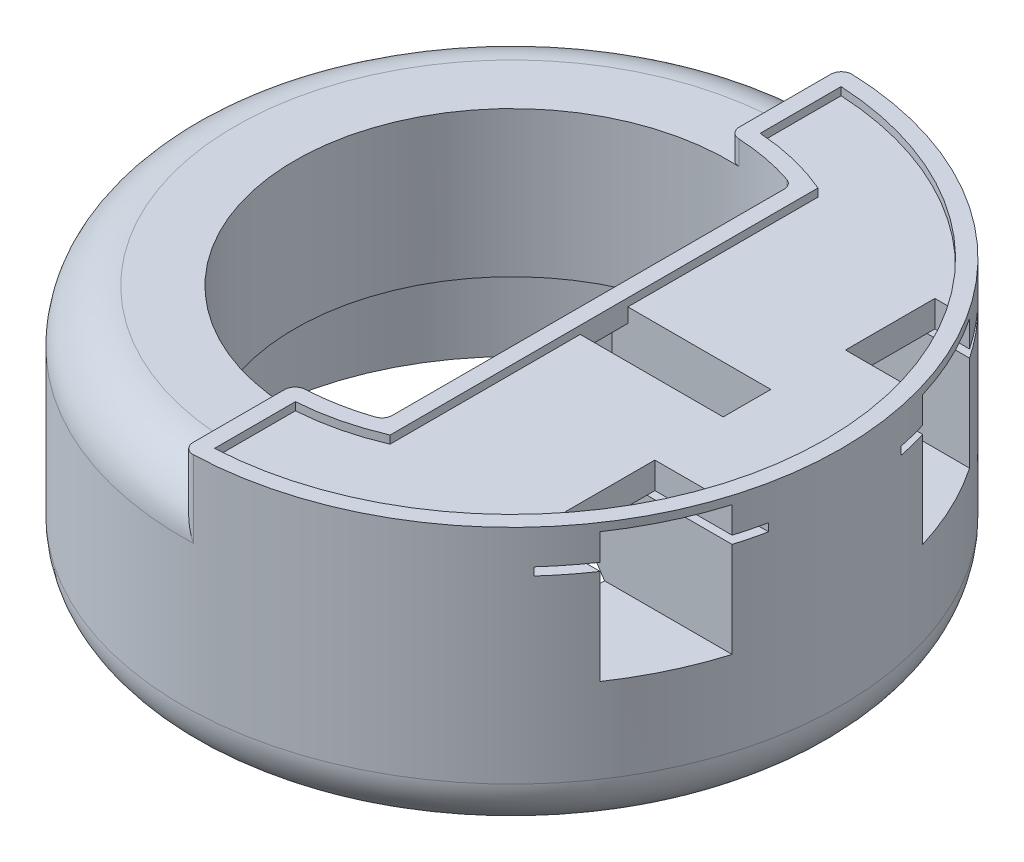
SolidWorks part; units mm, degrees
ref_plane "Plano frontal" through (0, 0, 0) normal (0, 0, 1) x (1, 0, 0)
ref_plane "Plano superior" through (0, 0, 0) normal (0, 1, 0) x (1, 0, 0)
ref_plane "Plano direito" through (0, 0, 0) normal (1, 0, 0) x (0, 0, -1)
sketch "Esboço1" plane through (0, 0, 0) normal (0, 1, 0) x (1, 0, 0)
  line L0 (14.4, 45.0022) -> (14.4, -45.0022)
  arc A0 (14.4, -45.0022) -> (14.4, 45.0022) centre (0, 0) ccw
  dimension "D1" = 94.5
  dimension "D2" = 14.4
extrude "Ressalto-extrusão1" add sketch "Esboço1" along normal blind 5
sketch "Esboço2" plane through (0, 5, 0) normal (0, 1, 0) x (1, 0, 0)
  line L0 (14.4, 4.5) -> (44.4, 4.5)
  line L1 (14.4, 45.0022) -> (14.4, -45.0022) construction
  line L2 (44.4, 4.5) -> (44.4, -4.5)
  line L3 (44.4, -4.5) -> (14.4, -4.5)
  line L4 (14.4, -4.5) -> (14.4, 4.5)
  line L5 (14.4, 0) -> (47.25, 0) construction
  arc A1 (14.4, -45.0022) -> (14.4, 45.0022) centre (0, 0) ccw construction
  dimension "D1" = 9
  dimension "D2" = 30
extrude "Corte-extrusão1" cut sketch "Esboço2" against normal through all
sketch "Esboço3" plane through (0, 0, 0) normal (0, 0, 1) x (1, 0, 0)
  line L0 (47.189, 0) -> (42.8221, -13)
  line L1 (14.4, 0) -> (47.25, 0) construction
  line L2 (32.189, -5.4942) -> (35.189, 0)
  line L3 (36.6836, -13.0289) -> (42.8221, -13)
  line L4 (35.189, 0) -> (47.189, 0)
  arc A0 (32.189, -5.4942) -> (36.6836, -13.0289) centre (36.6596, -7.9353) ccw
  circle A2 centre (36.6596, -7.9353) radius 2.35
  dimension "D1" = 12
  dimension "D2" = 13
  dimension "D3" = 3
extrude "Ressalto-extrusão2" add sketch "Esboço3" along normal blind 8 from offset 4.5
mirror "Espelhar1" about plane through (0, 0, 0) normal (0, 0, 1) of "Ressalto-extrusão2"
sketch "Esboço4" plane through (0, 5, 0) normal (0, 1, 0) x (1, 0, 0)
  line L0 (14.4, 45.0022) -> (15.9238, 49.7644)
  line L1 (14.4, -45.0022) -> (15.9238, -49.7644)
  arc A0 (14.4, -45.0022) -> (14.4, 45.0022) centre (0, 0) ccw construction
  arc A1 (14.4, -45.0022) -> (14.4, 45.0022) centre (0, 0) ccw
  arc A2 (15.9238, -49.7644) -> (15.9238, 49.7644) centre (0, 0) ccw
  dimension "D1" = 5
extrude "Corte-extrusão2" cut sketch "Esboço4" against normal through all
fillet "Filete1" radius 5 2 edges at (42.8221, -13, -8.5) (42.8221, -13, 8.5)
chamfer "Chanfro1" [suppressed] distance 5 angle 45
sketch "Esboço5" [suppressed] plane through (0, 0, 0) normal (0, 0, 1) x (1, 0, 0)
  line L0 (16.9, 2.5) -> (16.9, 0)
  line L1 (19.4, 5) -> (14.4, 0) construction
  line L2 (14.4, 0) -> (45.5666, 0) construction
  line L3 (16.9, 0) -> (14.4, 0)
  line L4 (14.4, 0) -> (16.9, 2.5)
  dimension "D1" = 2.5
extrude "Corte-extrusão3" [suppressed] cut sketch "Esboço5" against normal through all both and the other way through all
ref_plane "Plano1" through (0, -5.5, 0) normal (0, -1, 0) x (-1, 0, 0)
sketch "Esboço7" plane through (0, -5.5, 0) normal (0, -1, 0) x (-1, 0, 0)
  line L0 (-14.5, 44.9701) -> (-14.5, 4.5)
  line L1 (-33.5473, -4.5) -> (-33.5473, -33.2738)
  line L2 (-14.4, -4.5) -> (-44.4, -4.5) construction
  line L3 (-33.5473, 4.5) -> (-33.5473, 33.2738)
  line L4 (-44.4, 4.5) -> (-14.4, 4.5) construction
  line L5 (-33.5473, 4.5) -> (-14.5, 4.5)
  line L6 (-33.5473, -4.5) -> (-14.5, -4.5)
  line L7 (-14.5, -4.5) -> (-14.5, -44.9701)
  arc A0 (-14.5, 44.9701) -> (-33.5473, 33.2738) centre (0, 0) ccw
  arc A1 (-33.5473, -33.2738) -> (-14.5, -44.9701) centre (0, 0) ccw
  dimension "D1" = 94.5
  dimension "D2" = 14.5
  dimension "D3" = 19.0473
extrude "Ressalto-extrusão4" add sketch "Esboço7" along normal blind 20
sketch "Esboço8" plane through (0, -25.5, 0) normal (0, -1, 0) x (1, 0, 0)
  line L0 (33.5473, -33.2738) -> (33.5473, 33.2738)
  line L2 (14.5, 44.9701) -> (14.5, -44.9701)
  arc A0 (33.5473, 33.2738) -> (14.5, 44.9701) centre (0, 0) ccw
  arc A1 (14.5, -44.9701) -> (33.5473, -33.2738) centre (0, 0) ccw
  dimension "D1" = 94.5
  dimension "D2" = 33.5473
extrude "Ressalto-extrusão5" add sketch "Esboço8" against normal blind 4
sketch "Esboço9" plane through (0, -25.5, 0) normal (0, -1, 0) x (1, 0, 0)
  line L0 (33.5473, -33.2738) -> (33.5473, 33.2738) construction
  line L1 (33.5473, -33.2738) -> (33.5473, 33.2738)
  arc A0 (14.4, -45.0022) -> (45.5666, -12.5) centre (0, 0) ccw construction
  arc A1 (45.5666, -12.5) -> (47.0352, -4.5) centre (0, 0) ccw construction
  arc A2 (47.0352, -4.5) -> (47.0352, 4.5) centre (0, 0) ccw construction
  arc A3 (47.0352, 4.5) -> (45.5666, 12.5) centre (0, 0) ccw construction
  arc A4 (45.5666, 12.5) -> (14.4, 45.0022) centre (0, 0) ccw construction
  arc A5 (33.5473, -33.2738) -> (45.5666, -12.5) centre (0, 0) ccw
  arc A6 (45.5666, -12.5) -> (47.0352, -4.5) centre (0, 0) ccw
  arc A7 (47.0352, -4.5) -> (47.0352, 4.5) centre (0, 0) ccw
  arc A8 (47.0352, 4.5) -> (45.5666, 12.5) centre (0, 0) ccw
  arc A9 (45.5666, 12.5) -> (33.5473, 33.2738) centre (0, 0) ccw
extrude "Ressalto-extrusão6" add sketch "Esboço9" against normal up to surface (4 mm away) up to face at (24.0236, -21.5, 0)
fillet "Filete2" radius 5 2 edges at (33.5473, -11.9675, -8.5) (33.5473, -11.9675, 8.5)
sketch "Esboço10" plane through (0, 0, 0) normal (0, 0, 1) x (1, 0, 0)
  line L0 (14.5, -10.5) -> (24.5, -25.5)
  line L1 (24.5, -25.5) -> (14.5, -25.5)
  line L3 (14.5, -25.5) -> (14.5, -10.5)
  dimension "D1" = 10
  dimension "D2" = 15
  dimension "D3" = 56.31
extrude "Corte-extrusão4" cut sketch "Esboço10" against normal through all both and the other way through all
sketch "Esboço12" plane through (0, -25.5, 0) normal (0, -1, 0) x (1, 0, 0)
  circle A0 centre (0, 0) radius 65
  circle A1 centre (0, 0) radius 41
  dimension "D1" = 130
  dimension "D2" = 24
extrude "Ressalto-extrusão7" add sketch "Esboço12" against normal up to surface (20 mm away) up to face at (26.8613, -5.5, -18.8977)
sketch "Esboço13" plane through (0, -5.5, 0) normal (0, 1, 0) x (1, 0, 0)
  line L0 (33.5473, 12.5) -> (39.048, 12.5)
  line L1 (33.5473, 23.5707) -> (33.5473, 12.5) construction
  line L2 (33.5473, 23.5707) -> (33.5473, 12.5)
  line L3 (0, 0) -> (-33.611, 0) construction
  line L4 (33.5473, -23.5707) -> (33.5473, -12.5)
  line L5 (33.5473, -12.5) -> (39.048, -12.5)
  arc A0 (39.048, 12.5) -> (33.5473, 23.5707) centre (0, 0) ccw construction
  arc A1 (39.048, 12.5) -> (33.5473, 23.5707) centre (0, 0) ccw
  arc A2 (39.048, -12.5) -> (33.5473, -23.5707) centre (0, 0) cw
extrude "Ressalto-extrusão8" add sketch "Esboço13" against normal up to surface (20 mm away) up to face at (-8.25, -25.5, 0)
sketch "Esboço14" plane through (0, 5, 0) normal (0, 1, 0) x (1, 0, 0)
  line L0 (14.4, 45.0022) -> (14.4, 60.5616)
  line L1 (14.4, -45.0022) -> (14.4, -60.5616)
  arc A0 (14.4, -45.0022) -> (14.4, 45.0022) centre (0, 0) ccw construction
  arc A1 (14.4, -45.0022) -> (14.4, 45.0022) centre (0, 0) ccw
  arc A2 (14.4, -60.5616) -> (14.4, 60.5616) centre (0, 0) ccw
  arc A3 (18.9714, -59.2887) -> (18.9714, 59.2887) centre (0, 0) ccw construction
  dimension "D1" = 15
extrude "Ressalto-extrusão9" add sketch "Esboço14" against normal up to surface (5 mm away) up to face at (29.7731, 0, -16.5908)
sketch "Esboço16" plane through (0, -5.5, 0) normal (0, 1, 0) x (1, 0, 0)
  line L0 (14.4, 60.5616) -> (14.4, 4.5) construction
  line L1 (14.4, 60.5616) -> (14.4, 38.388)
  line L2 (14.4, -4.5) -> (14.4, -60.5616) construction
  line L3 (14.4, -38.388) -> (14.4, -60.5616)
  arc A0 (14.4, 60.5616) -> (14.4, -60.5616) centre (0, 0) ccw
  arc A1 (14.4, 38.388) -> (14.4, -38.388) centre (0, 0) ccw
  dimension "D1" = 41
extrude "Ressalto-extrusão10" add sketch "Esboço16" along normal up to surface (10.5 mm away) up to face at (32.375, 5, 0)
sketch "Esboço17" plane through (0, -5.5, 0) normal (0, 1, 0) x (1, 0, 0)
  circle A0 centre (0, 0) radius 62.25
  circle A1 centre (0, 0) radius 65 construction
  circle A2 centre (0, 0) radius 65
  dimension "D1" = 124.5
extrude "Corte-extrusão5" cut sketch "Esboço17" against normal through all
sketch "Esboço18" plane through (0, 5, 0) normal (0, 1, 0) x (1, 0, 0)
  line L0 (39.0096, 4.5) -> (44.4, 4.5)
  line L1 (44.4, -4.5) -> (44.4, 4.5) construction
  line L2 (45.3415, 4.5) -> (40.7523, 4.5) construction
  line L3 (44.4, 4.5) -> (44.4, -4.5)
  line L4 (44.4, -4.5) -> (39.0096, -4.5)
  line L6 (39.0096, 4.5) -> (39.0096, -4.5)
extrude "Corte-extrusão6" cut sketch "Esboço18" against normal up to surface (26.5 mm away) up to face at (32.238, -21.5, 0)
sketch "Esboço19" plane through (0, -5.5, 0) normal (0, 1, 0) x (1, 0, 0)
  line L0 (14.4, 4.5) -> (35.189, 4.5)
  line L4 (14.4, 4.5) -> (14.4, 38.388)
  line L5 (0, 0) -> (-73.7053, 0) construction
  line L6 (14.4, -4.5) -> (35.189, -4.5)
  line L8 (14.4, -4.5) -> (14.4, -38.388)
  line L9 (35.189, -4.5) -> (35.189, -21.0413)
  line L11 (35.189, 4.5) -> (35.189, 21.0413)
  arc A0 (24.5, 32.8748) -> (14.5, 38.3504) centre (0, 0) ccw construction
  arc A1 (35.189, 21.0413) -> (14.4, 38.388) centre (0, 0) ccw
  arc A2 (35.189, -21.0413) -> (14.4, -38.388) centre (0, 0) cw
extrude "Ressalto-extrusão12" add sketch "Esboço19" along normal up to surface (5.5 mm away) separate body up to face at (34.3346, 0, 0)
sketch "Esboço20" plane through (0, 5, 0) normal (0, 1, 0) x (1, 0, 0)
  circle A0 centre (0, 0) radius 62.25
extrude "Corte-extrusão7" cut sketch "Esboço20" against normal blind 3
sketch "Esboço21" plane through (0, 2, 0) normal (0, 1, 0) x (1, 0, 0)
  line L0 (0, -41) -> (0, -62.25)
  line L1 (0, 0) -> (-62.25, 0) construction
  line L2 (0, 41) -> (0, 62.25)
  line L3 (14.4, 4.5) -> (44.4, 4.5) construction
  line L4 (14.4, 38.388) -> (14.4, 4.5) construction
  line L5 (44.4, -4.5) -> (14.4, -4.5) construction
  line L6 (14.4, -4.5) -> (14.4, -38.388) construction
  line L7 (14.4, 4.5) -> (44.4, 4.5)
  line L8 (14.4, 38.388) -> (14.4, 4.5)
  line L9 (44.4, -4.5) -> (14.4, -4.5)
  line L10 (14.4, -4.5) -> (14.4, -38.388)
  line L11 (44.4, -4.5) -> (44.4, 4.5)
  arc A0 (0, -62.25) -> (0, 62.25) centre (0, 0) ccw
  arc A1 (14.4, 38.388) -> (14.4, -38.388) centre (0, 0) ccw construction
  arc A2 (14.4, 38.388) -> (0, 41) centre (0, 0) ccw
  arc A3 (0, -41) -> (14.4, -38.388) centre (0, 0) ccw
extrude "Ressalto-extrusão13" add sketch "Esboço21" along normal blind 3 contours L0 A0 L2 A2 L8 L7 L11 L9 L10 A3
sketch "Esboço23" plane through (0, -5.5, 0) normal (0, 1, 0) x (1, 0, 0)
  line L0 (51.5592, -34.8814) -> (16, -35)
  line L1 (16, -35) -> (16, -18)
  line L2 (16, -18) -> (66, -18)
  line L3 (66, -18) -> (66, -35)
  line L4 (66, -35) -> (51.5592, -34.8814)
  arc A0 (14.4, -60.5616) -> (14.4, 60.5616) centre (0, 0) ccw construction
extrude "Corte-extrusão8" cut sketch "Esboço23" against normal blind 14 and the other way up to surface other way up to face at (34.3346, 0, 0)
sketch "Esboço24" plane through (0, -5.5, 0) normal (0, -1, 0) x (1, 0, 0)
  line L0 (20.5, 18) -> (10.5, 18)
  line L1 (10.5, 18) -> (10.5, 34.985)
  line L2 (10.5, 34.985) -> (20.5, 34.985)
  line L3 (20.5, 34.985) -> (20.5, 18)
  dimension "D1" = 10
extrude "Corte-extrusão9" cut sketch "Esboço24" along normal up to surface (14 mm away) up to face at (38.1968, -19.5, 26.5424)
sketch "Esboço25" plane through (0, -5.5, 0) normal (0, -1, 0) x (1, 0, 0)
  line L0 (14.5, 18) -> (35.189, 18)
  line L1 (59.5908, 18) -> (14.5, 18) construction
  line L2 (35.189, 21.0413) -> (35.189, 4.5) construction
  line L3 (35.189, 18) -> (35.189, 21.0413)
  line L4 (14.5, 18) -> (14.5, 34.985)
  line L5 (14.5, 34.985) -> (21.3927, 34.9765)
  arc A0 (35.189, 21.0413) -> (14.4, 38.388) centre (0, 0) ccw construction
  arc A1 (35.189, 21.0413) -> (21.3927, 34.9765) centre (0, 0) ccw
extrude "Corte-extrusão10" cut sketch "Esboço25" against normal up to surface (5.5 mm away) up to face at (34.3346, 0, 0)
sketch "Esboço26" plane through (14.5, 0, 0) normal (1, 0, 0) x (0, 0, -1)
  line L0 (-34.9765, 0) -> (-18, 0)
  line L1 (-18, 0) -> (-18, -5.5)
  line L2 (-26.3175, -5.5) -> (26.3175, -5.5) construction
  line L3 (-18, 0) -> (-18, -5.5) construction
  line L4 (-18, -5.5) -> (-34.985, -5.5)
  line L5 (-34.985, 0) -> (-34.985, -5.5) construction
  line L6 (-34.985, -5.5) -> (-34.9765, 0)
extrude "Corte-extrusão11" cut sketch "Esboço26" against normal blind 5
sketch "Esboço27" plane through (0, -5.5, 0) normal (0, 1, 0) x (1, 0, 0)
  line L0 (35.189, -12.5) -> (14.4, -12.5)
  line L1 (14.4, -4.5) -> (14.4, -38.388) construction
  line L2 (14.4, -12.5) -> (14.4, -38.388)
  line L3 (35.189, -12.5) -> (39.048, -12.5)
  arc A0 (14.4, -38.388) -> (21.3927, -34.9765) centre (0, 0) ccw construction
  arc A1 (14.4, -38.388) -> (39.048, -12.5) centre (0, 0) ccw
extrude "Corte-extrusão12" cut sketch "Esboço27" along normal up to surface (5.5 mm away) up to face at (34.3346, 0, 0)
mirror "Espelhar3" about plane through (0, 0, 0) normal (0, 0, 1) of "Corte-extrusão8"
mirror "Espelhar4" about plane through (0, 0, 0) normal (0, 0, 1) of "Corte-extrusão9"
sketch "Esboço28" plane through (0, 0, -12.5) normal (0, 0, -1) x (-1, 0, 0)
  line L0 (-35.189, 0) -> (-35.189, -5.5)
  line L1 (-26.3175, -5.5) -> (26.3175, -5.5) construction
  line L2 (-35.189, 0) -> (-35.189, -5.5) construction
  line L3 (-35.189, -5.5) -> (-8.0032, -5.5)
  line L4 (-8.0032, -5.5) -> (-8.0032, 0)
  line L5 (-8.0032, 0) -> (-35.189, 0)
  dimension "D1" = 27.1857
extrude "Corte-extrusão13" cut sketch "Esboço28" along normal up to vertex (25.888 mm away) up to point (14.4, -5.5, -38.388)
sketch "Esboço29" plane through (0, 5, 0) normal (0, 1, 0) x (1, 0, 0)
  line L0 (63, 34.88) -> (45, 34.88)
  line L1 (45, 34.88) -> (45, 18)
  line L2 (45, 18) -> (63, 18)
  line L3 (63, 18) -> (63, 34.88)
  line L4 (0, 0) -> (66.1862, 0) construction
  line L5 (63, -18) -> (63, -34.88)
  line L6 (45, -18) -> (63, -18)
  line L7 (45, -34.88) -> (45, -18)
  line L8 (63, -34.88) -> (45, -34.88)
  dimension "D1" = 16.88
  dimension "D2" = 18
  dimension "D3" = 18
  dimension "D4" = 45
extrude "Corte-extrusão14" cut sketch "Esboço29" against normal up to surface (5 mm away) up to face at (34.3346, 0, 0)
sketch "Esboço30" plane through (0, 5, 0) normal (0, 1, 0) x (1, 0, 0)
  line L1 (3, 59.174) -> (3, 43.8976)
  line L2 (17.4, 40.4134) -> (17.4, 7.5)
  line L6 (17.4, 7.5) -> (17.4, -40.4134)
  line L7 (3, -43.8976) -> (3, -59.174)
  line L13 (45, 34.88) -> (51.5601, 34.88)
  line L14 (0, 62.25) -> (0, 41)
  line L15 (14.4, 38.388) -> (14.4, 4.5)
  line L16 (14.4, 4.5) -> (44.4, 4.5)
  line L17 (44.4, 4.5) -> (44.4, -4.5)
  line L18 (44.4, -4.5) -> (14.4, -4.5)
  line L19 (14.4, -4.5) -> (14.4, -38.388)
  line L20 (0, -41) -> (0, -62.25)
  line L21 (51.5601, -34.88) -> (45, -34.88)
  line L22 (45, -34.88) -> (45, -18)
  line L23 (45, -18) -> (59.5908, -18)
  line L24 (59.5908, 18) -> (45, 18)
  line L25 (45, 18) -> (45, 34.88)
  line L27 (0, 62.25) -> (0, 41)
  line L28 (14.4, 38.388) -> (14.4, 4.5)
  line L32 (14.4, 4.5) -> (14.4, -38.388)
  line L33 (0, -41) -> (0, -62.25)
  line L39 (14.4, -4.5) -> (14.4, -38.388) construction
  line L40 (17.4, -7.5) -> (17.4, -40.4134) construction
  line L52 (44.4, -4.5) -> (14.4, -4.5) construction
  line L53 (47.4, -7.5) -> (17.4, -7.5) construction
  line L54 (47.4, 7.5) -> (47.4, -7.5) construction
  line L55 (44.4, 4.5) -> (44.4, -4.5) construction
  line L56 (14.4, 4.5) -> (44.4, 4.5) construction
  line L57 (17.4, 7.5) -> (47.4, 7.5) construction
  line L60 (51.5601, -34.88) -> (45, -34.88) construction
  line L61 (45.5595, -37.88) -> (42, -37.88) construction
  line L62 (42, -37.88) -> (42, -15) construction
  line L63 (45, -34.88) -> (45, -18) construction
  line L64 (45, -18) -> (59.5908, -18) construction
  line L65 (42, -15) -> (57.3198, -15) construction
  line L66 (57.3198, 15) -> (42, 15) construction
  line L67 (42, 15) -> (42, 37.88) construction
  line L68 (59.5908, 18) -> (45, 18) construction
  line L69 (45, 18) -> (45, 34.88) construction
  line L70 (42, 37.88) -> (45.5595, 37.88) construction
  line L71 (45, 34.88) -> (51.5601, 34.88) construction
  arc A0 (57.3198, 15) -> (3, 59.174) centre (0, 0) ccw
  arc A1 (17.4, 40.4134) -> (3, 43.8976) centre (0, 0) ccw
  arc A2 (3, -43.8976) -> (17.4, -40.4134) centre (0, 0) ccw
  arc A3 (3, -59.174) -> (57.3198, -15) centre (0, 0) ccw
  arc A4 (57.3198, -15) -> (57.3198, 15) centre (0, 0) ccw
  arc A5 (51.5601, 34.88) -> (0, 62.25) centre (0, 0) ccw
  arc A6 (14.4, 38.388) -> (0, 41) centre (0, 0) ccw
  arc A7 (0, -41) -> (14.4, -38.388) centre (0, 0) ccw
  arc A8 (0, -62.25) -> (51.5601, -34.88) centre (0, 0) ccw
  arc A9 (59.5908, -18) -> (59.5908, 18) centre (0, 0) ccw
  arc A10 (59.5908, 18) -> (0, 62.25) centre (0, 0) ccw
  arc A11 (14.4, 38.388) -> (0, 41) centre (0, 0) ccw
  arc A12 (0, -41) -> (14.4, -38.388) centre (0, 0) ccw
  arc A13 (0, -62.25) -> (59.5908, -18) centre (0, 0) ccw
  arc A14 (59.5908, -18) -> (59.5908, 18) centre (0, 0) ccw
  arc A15 (51.5601, 34.88) -> (0, 62.25) centre (0, 0) ccw construction
  arc A16 (45.5595, 37.88) -> (3, 59.174) centre (0, 0) ccw construction
  arc A17 (0, -62.25) -> (51.5601, -34.88) centre (0, 0) ccw construction
  arc A18 (3, -59.174) -> (45.5595, -37.88) centre (0, 0) ccw construction
  dimension "D1" = 0
  dimension "D2" = 3
extrude "Ressalto-extrusão15" add sketch "Esboço30" along normal blind 1.5
sketch "Esboço31" plane through (0, -5.5, 0) normal (0, 1, 0) x (1, 0, 0)
  line L5 (16, -34.985) -> (14.5, -34.985)
  line L6 (14.5, -34.985) -> (14.5, -38.3504)
  line L7 (14.4, -38.388) -> (14.4, -60.5616)
  line L8 (51.5592, -34.8814) -> (16, -35)
  line L9 (16, -35) -> (16, -34.985)
  line L10 (16, -34.985) -> (14.5, -34.985)
  line L11 (14.5, -34.985) -> (14.5, -38.3504)
  line L12 (14.4, -38.388) -> (14.4, -60.5616)
  line L13 (51.5592, -34.8814) -> (16, -35)
  line L14 (16, -35) -> (16, -34.985)
  line L15 (14.5, 38.3504) -> (14.5, 34.985)
  line L16 (14.5, 34.985) -> (16, 34.985)
  line L17 (16, 34.985) -> (16, 35)
  line L18 (16, 35) -> (51.5592, 34.8814)
  line L19 (14.4, 60.5616) -> (14.4, 38.388)
  line L20 (14.5, 38.3504) -> (14.5, 34.985)
  line L21 (14.5, 34.985) -> (16, 34.985)
  line L22 (16, 34.985) -> (16, 35)
  line L23 (16, 35) -> (51.5592, 34.8814)
  line L24 (14.4, 60.5616) -> (14.4, 38.388)
  arc A2 (14.4, -38.388) -> (14.5, -38.3504) centre (0, 0) ccw
  arc A3 (14.4, -60.5616) -> (51.5592, -34.8814) centre (0, 0) ccw
  arc A4 (14.4, -38.388) -> (14.5, -38.3504) centre (0, 0) ccw
  arc A5 (14.4, -60.5616) -> (51.5592, -34.8814) centre (0, 0) ccw
  arc A6 (51.5592, 34.8814) -> (14.4, 60.5616) centre (0, 0) ccw
  arc A7 (14.5, 38.3504) -> (14.4, 38.388) centre (0, 0) ccw
  arc A8 (51.5592, 34.8814) -> (14.4, 60.5616) centre (0, 0) ccw
  arc A9 (14.5, 38.3504) -> (14.4, 38.388) centre (0, 0) ccw
  dimension "D1" = 0
  dimension "D2" = 0
extrude "Ressalto-extrusão16" add sketch "Esboço31" along normal blind 4
sketch "Esboço32" plane through (0, -1.5, 0) normal (0, 1, 0) x (1, 0, 0)
  line L0 (51.5601, -34.88) -> (51.5601, -41.8803) construction
  line L1 (46.0554, -41.8803) -> (14.4, -41.8803)
  line L2 (14.4, -38.388) -> (14.4, -60.5616) construction
  line L3 (14.4, -41.8803) -> (14.4, -60.5616)
  line L4 (46.0554, -41.8803) -> (51.5601, -41.8803) construction
  arc A1 (0, -62.25) -> (0, 62.25) centre (0, 0) ccw construction
  arc A2 (14.4, -60.5616) -> (46.0554, -41.8803) centre (0, 0) ccw
  arc A3 (51.5601, -34.88) -> (0, 62.25) centre (0, 0) ccw
  line M10 (14.4, -38.388) -> (14.4, -60.5616)
  arc M11 (14.4, -60.5616) -> (51.5592, -34.8814) centre (0, 0) ccw
  dimension "D1" = 7.0003
extrude "Ressalto-extrusão17" add sketch "Esboço32" along normal up to surface (1.5 mm away) contours L1 M11 M10 region at (26.0479, -1.5, 48.8714) up to face at (37.9704, 0, 0)
mirror "Espelhar5" about plane through (0, 0, 0) normal (0, 0, 1) of "Ressalto-extrusão16", "Ressalto-extrusão17"
sketch "Esboço33" plane through (0, -5.5, 0) normal (0, 1, 0) x (1, 0, 0)
  line L15 (59.5908, 18) -> (14.5, 18)
  line L16 (14.5, 18) -> (14.5, 4.5)
  line L17 (14.5, 4.5) -> (32.1858, 4.5)
  line L18 (32.1858, 4.5) -> (32.1858, 12.5)
  line L19 (32.1858, 12.5) -> (45.3415, 12.5)
  line L20 (45.3415, 12.5) -> (45.3415, 4.5)
  line L21 (45.3415, 4.5) -> (44.4, 4.5)
  line L22 (44.4, 4.5) -> (44.4, -4.5)
  line L23 (44.4, -4.5) -> (45.3415, -4.5)
  line L24 (45.3415, -4.5) -> (45.3415, -12.5)
  line L25 (45.3415, -12.5) -> (32.1858, -12.5)
  line L26 (32.1858, -12.5) -> (32.1858, -4.5)
  line L27 (32.1858, -4.5) -> (14.5, -4.5)
  line L28 (14.5, -4.5) -> (14.5, -18)
  line L29 (14.5, -18) -> (59.5908, -18)
  line L30 (59.5908, 18) -> (14.5, 18)
  line L31 (14.5, 18) -> (14.5, 4.5)
  line L32 (14.5, 4.5) -> (32.1858, 4.5)
  line L33 (32.1858, 4.5) -> (32.1858, 12.5)
  line L34 (32.1858, 12.5) -> (45.3415, 12.5)
  line L35 (45.3415, 12.5) -> (45.3415, 4.5)
  line L36 (45.3415, 4.5) -> (44.4, 4.5)
  line L37 (44.4, 4.5) -> (44.4, -4.5)
  line L38 (44.4, -4.5) -> (45.3415, -4.5)
  line L39 (45.3415, -4.5) -> (45.3415, -12.5)
  line L40 (45.3415, -12.5) -> (32.1858, -12.5)
  line L41 (32.1858, -12.5) -> (32.1858, -4.5)
  line L42 (32.1858, -4.5) -> (14.5, -4.5)
  line L43 (14.5, -4.5) -> (14.5, -18)
  line L44 (14.5, -18) -> (59.5908, -18)
  arc A1 (59.5908, -18) -> (59.5908, 18) centre (0, 0) ccw
  arc A2 (59.5908, -18) -> (59.5908, 18) centre (0, 0) ccw
  dimension "D1" = 0
extrude "Ressalto-extrusão18" add sketch "Esboço33" along normal up to surface (4 mm away) up to face at (23.4425, -1.5, 37.5561)
sketch "Esboço34" plane through (0, -1.5, 0) normal (0, 1, 0) x (1, 0, 0)
  line L0 (45.5666, 12.5) -> (60.9821, 12.5)
  line L1 (45.5666, -12.5) -> (60.9821, -12.5)
  line L2 (47.0352, 4.5) -> (44.4, 4.5)
  line L3 (44.4, 4.5) -> (44.4, -4.5)
  line L4 (44.4, -4.5) -> (47.0352, -4.5)
  arc A0 (0, -62.25) -> (0, 62.25) centre (0, 0) ccw construction
  arc A1 (60.9821, -12.5) -> (60.9821, 12.5) centre (0, 0) ccw
  arc A2 (47.0352, 4.5) -> (45.5666, 12.5) centre (0, 0) ccw construction
  arc A3 (47.0352, 4.5) -> (45.5666, 12.5) centre (0, 0) ccw
  arc A4 (45.5666, -12.5) -> (47.0352, -4.5) centre (0, 0) ccw construction
  arc A5 (45.5666, -12.5) -> (47.0352, -4.5) centre (0, 0) ccw
extrude "Ressalto-extrusão19" add sketch "Esboço34" along normal up to surface (1.5 mm away) up to face at (39.0032, 0, 0)
sketch "Esboço35" plane through (0, 0, 4.5) normal (0, 0, -1) x (-1, 0, 0)
  line L0 (-33.5473, -21.5) -> (-33.5473, -18.0202) construction
  line L1 (-38.5237, -13.0202) -> (-39.245, -13.0168) construction
  line L2 (-40.7523, -12.7768) -> (-40.7523, -21.5) construction
  line L3 (-33.5473, -21.5) -> (-33.5473, -18.0202)
  line L4 (-38.5237, -13.0202) -> (-39.245, -13.0168)
  line L5 (-40.7523, -12.7768) -> (-40.7523, -21.5)
  line L6 (-40.7523, -21.5) -> (-33.5473, -21.5)
  arc A0 (-40.7523, -12.7768) -> (-39.245, -13.0168) centre (-39.2215, -8.0169) ccw construction
  arc A1 (-33.5473, -18.0202) -> (-38.5237, -13.0202) centre (-38.5473, -18.0202) ccw construction
  arc A2 (-40.7523, -12.7768) -> (-39.245, -13.0168) centre (-39.2215, -8.0169) ccw
  arc A3 (-33.5473, -18.0202) -> (-38.5237, -13.0202) centre (-38.5473, -18.0202) ccw
extrude "Ressalto-extrusão20" add sketch "Esboço35" against normal up to vertex up to point (33.5473, -21.5, 12.5)
mirror "Espelhar6" about plane through (0, 0, 0) normal (0, 0, 1) of "Ressalto-extrusão20"
sketch "Esboço36" plane through (44.4, 0, 0) normal (-1, 0, 0) x (0, 0, 1)
  line L0 (-4.5, -21.5) -> (4.5, -21.5) construction
  line L1 (-3.5, -11.5) -> (3.5, -11.5)
  line L2 (-3.5, -11.5) -> (-3.5, -21.5)
  line L3 (-3.5, -21.5) -> (3.5, -21.5)
  line L4 (3.5, -11.5) -> (3.5, -21.5)
  line L5 (0, -11.5) -> (0, 0) construction
  dimension "D1" = 7
  dimension "D2" = 10
extrude "Corte-extrusão15" cut sketch "Esboço36" against normal blind 15
sketch "Esboço37" plane through (0, 0, 0) normal (0, 0, 1) x (1, 0, 0)
  line L0 (24.5, -25.5) -> (39.5, -25.5)
  line L1 (-62.25, -25.5) -> (62.25, -25.5) construction
  line L2 (39.5, -25.5) -> (29.5, -10.5)
  line L3 (29.5, -10.5) -> (14.5, -10.5)
  line L4 (14.5, -10.5) -> (24.5, -25.5) construction
  line L5 (14.5, -10.5) -> (24.5, -25.5) construction
  line L6 (14.5, -10.5) -> (14.5, -25.5)
  line L7 (-41, -25.5) -> (24.5, -25.5) construction
  line L8 (14.5, -25.5) -> (24.5, -25.5)
  dimension "D1" = 15
extrude "Corte-extrusão16" cut sketch "Esboço37" against normal up to vertex and the other way up to vertex up to point (14.5, -10.5, -38.3504) other way up to point (14.5, -10.5, 38.3504)
sketch "Esboço38" plane through (0, 5, 0) normal (0, -1, 0) x (1, 0, 0)
  line L4 (14.4, 4.5) -> (14.4, -4.5)
  line L5 (14.4, -4.5) -> (17.4, -4.5)
  line L6 (17.4, -4.5) -> (17.4, 4.5)
  line L7 (17.4, 4.5) -> (14.4, 4.5)
  line L8 (14.4, 4.5) -> (14.4, -4.5)
  line L9 (14.4, -4.5) -> (17.4, -4.5)
  line L10 (17.4, -4.5) -> (17.4, 4.5)
  line L11 (17.4, 4.5) -> (14.4, 4.5)
  dimension "D1" = 0
extrude "Ressalto-extrusão21" add sketch "Esboço38" along normal blind 2.7
sketch "Esboço41" plane through (0, -25.5, 0) normal (0, -1, 0) x (1, 0, 0)
  line L0 (14.5, 38.3504) -> (39.5, 38.3504) construction
  line L1 (39.5, -38.3504) -> (39.5, 38.3504) construction
  line L2 (39.5, -38.3504) -> (29.5, -38.3504) construction
  line L3 (29.5, -38.3504) -> (14.5, -38.3504) construction
  line L4 (14.5, 38.3504) -> (39.5, 38.3504)
  line L5 (39.5, -38.3504) -> (39.5, 38.3504)
  line L6 (39.5, -38.3504) -> (29.5, -38.3504)
  line L7 (29.5, -38.3504) -> (14.5, -38.3504)
  arc A0 (14.5, 38.3504) -> (14.5, -38.3504) centre (0, 0) ccw construction
  circle A1 centre (0, 0) radius 62.25
  circle A2 centre (0, 0) radius 62.25
  arc A3 (14.5, 38.3504) -> (14.5, -38.3504) centre (0, 0) ccw
  dimension "D1" = 0
extrude "Ressalto-extrusão23" add sketch "Esboço41" along normal blind 20
sketch "Esboço42" plane through (0, -45.5, 0) normal (0, -1, 0) x (1, 0, 0)
  circle A0 centre (0, 0) radius 55.0545
  circle A1 centre (0, 0) radius 50.8
  dimension "D1" = 101.6
extrude "Ressalto-extrusão24" add sketch "Esboço42" against normal blind 20
sketch "Esboço43" plane through (0, -45.5, 0) normal (0, -1, 0) x (1, 0, 0)
  circle A0 centre (0, 0) radius 50.8
  dimension "D1" = 101.6
extrude "Corte-extrusão18" cut sketch "Esboço43" against normal blind 20
fillet "Filete5" radius 10 2 edges at (0, -45.5, -62.25) (-62.25, 2, 0)
sketch "Esboço44" plane through (0, -25.5, 0) normal (0, -1, 0) x (1, 0, 0)
  line L0 (33.315, -38.3504) -> (4.381, -40.7653)
  line L1 (33.315, -38.3504) -> (14.5, -38.3504) construction
  line L2 (33.315, -38.3504) -> (14.5, -38.3504)
  arc A1 (14.5, 38.3504) -> (14.5, -38.3504) centre (0, 0) ccw construction
  arc A2 (4.381, -40.7653) -> (14.5, -38.3504) centre (0, 0) ccw
extrude "Corte-extrusão19" cut sketch "Esboço44" against normal blind 15
mirror "Espelhar7" about plane through (0, 0, 0) normal (0, 0, 1) of "Corte-extrusão19"
sketch "Esboço45" plane through (0, -25.5, 0) normal (0, -1, 0) x (1, 0, 0)
  line L0 (59.4, 3.5) -> (44.4, 3.5) construction
  line L1 (44.4, -3.5) -> (50.4, -3.5)
  line L2 (44.4, -3.5) -> (44.4, 3.5)
  line L3 (44.4, 3.5) -> (50.4, 3.5)
  line L4 (50.4, -3.5) -> (50.4, 3.5)
  dimension "D1" = 6
extrude "Corte-extrusão20" cut sketch "Esboço45" against normal blind 2
sketch "Esboço46" plane through (0, -23.5, 0) normal (0, -1, 0) x (1, 0, 0)
  circle A0 centre (48.1373, 0) radius 1.75
  dimension "D1" = 3.5
extrude "Corte-extrusão21" cut sketch "Esboço46" against normal up to surface and the other way through all up to face at (46.2583, -21.5, 0)
sketch "Esboço47" plane through (0, -11.5, 0) normal (0, -1, 0) x (1, 0, 0)
  line L4 (44.4, 3.5) -> (44.4, -3.5)
  line L5 (44.4, -3.5) -> (59.4, -3.5)
  line L6 (59.4, -3.5) -> (59.4, 3.5)
  line L7 (59.4, 3.5) -> (44.4, 3.5)
  line L8 (44.4, 3.5) -> (44.4, -3.5)
  line L9 (44.4, -3.5) -> (59.4, -3.5)
  line L10 (59.4, -3.5) -> (59.4, 3.5)
  line L11 (59.4, 3.5) -> (44.4, 3.5)
  dimension "D1" = 0
extrude "Ressalto-extrusão25" add sketch "Esboço47" along normal blind 6.5
sketch "Esboço48" plane through (0, -18, 0) normal (0, -1, 0) x (1, 0, 0)
  circle A0 centre (48.1373, 0) radius 1.75
extrude "Corte-extrusão22" cut sketch "Esboço48" against normal blind 5
fillet "Filete8" radius 2 2 edges at (14.4, 3.25, 38.388) (14.4, 3.25, -38.388)
fillet "Filete9" radius 2 4 edges at (0, 4.25, 41) (0, 4.25, -41) (0, -0.75, 62.25) (0, -0.75, -62.25)
equation "\"E\"=4"
